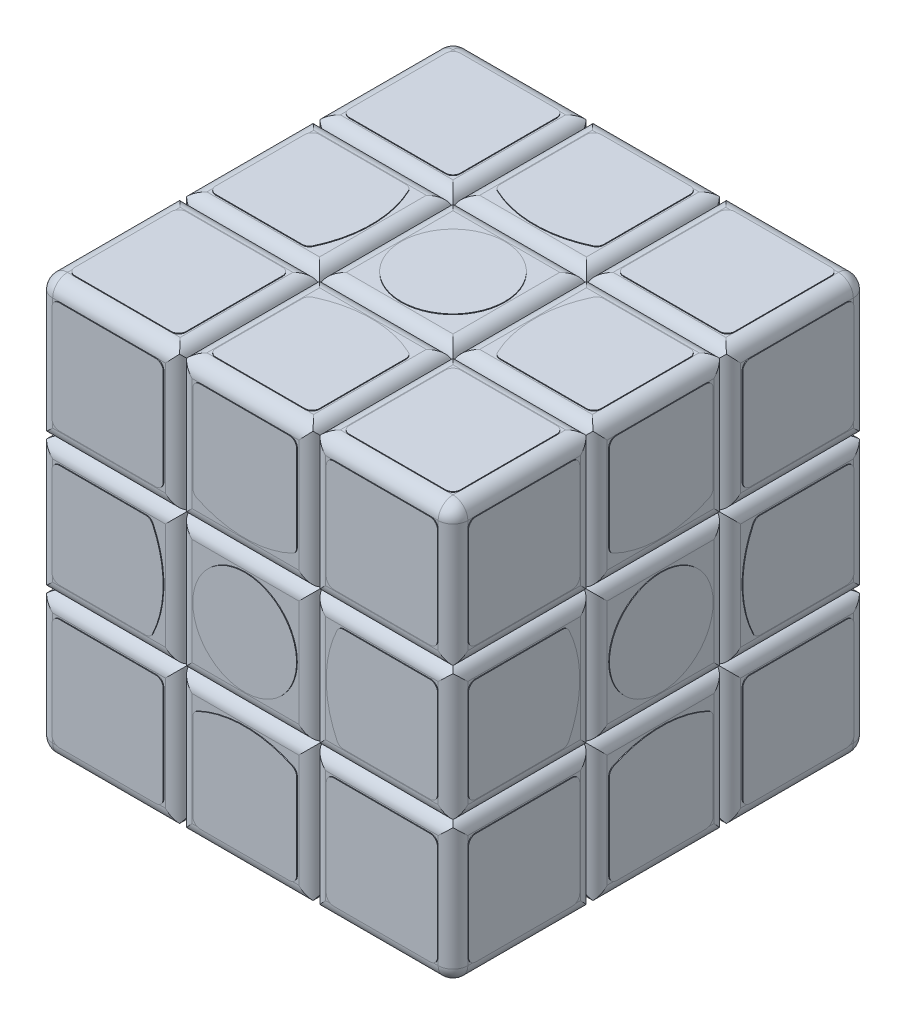
SolidWorks part; units mm, degrees
ref_plane "前视基准面" through (0, 0, 0) normal (0, 0, 1) x (1, 0, 0)
ref_plane "上视基准面" through (0, 0, 0) normal (0, 1, 0) x (1, 0, 0)
ref_plane "右视基准面" through (0, 0, 0) normal (1, 0, 0) x (0, 0, -1)
sketch "草图1" plane through (0, 0, 0) normal (0, 0, 1) x (1, 0, 0)
  line L5 (28, -28) -> (-28, -28)
  line L6 (28, -28) -> (28, 28)
  line L7 (28, 28) -> (-28, 28)
  line L8 (-28, -28) -> (-28, 28)
  line L9 (28, -28) -> (-28, 28) construction
  line L10 (28, 28) -> (-28, -28) construction
  point P0 (0, 0)
  dimension "D1" = 56
extrude "凸台-拉伸1" add sketch "草图1" along normal mid plane 56
fillet "圆角1" radius 2 12 edges at (0, 28, 28) (0, 28, -28) (28, 0, 28) (0, -28, 28) (-28, 0, 28) (0, -28, -28) (28, 0, -28) (-28, 0, -28) (28, 28, 0) (-28, 28, 0) (28, -28, 0) (-28, -28, 0)
sketch "草图2" plane through (0, 28, 0) normal (0, 1, 0) x (0, 0, -1)
  line L0 (0, 37.19) -> (0, -37.8051) construction
  line L1 (-9, 28) -> (-9, 9) construction
  line L2 (-26, 28) -> (26, 28) construction
  line L3 (-38.0373, 0) -> (42.2673, 0) construction
  line L5 (25, -7) -> (13.3509, -7)
  line L6 (-28, -26) -> (-28, 26) construction
  line L8 (-28, 9) -> (-9, 9) construction
  line L9 (25, 7) -> (13.3509, 7)
  line L10 (26, 6) -> (26, -6)
  line L11 (-28, 9) -> (-28, 26)
  line L18 (-26, 28) -> (-9, 28)
  line L19 (-25, 26) -> (-12, 26)
  line L20 (-11, 25) -> (-11, 12)
  line L21 (-25, 11) -> (-12, 11)
  line L26 (-26, 12) -> (-26, 25)
  line L27 (-11, 26) -> (-11, 11) construction
  line L28 (-26, 26) -> (-11, 26) construction
  line L29 (-26, 11) -> (-11, 11) construction
  line L51 (-26, 11) -> (-26, 26) construction
  line L52 (-7, -25) -> (-7, -13.3509)
  line L53 (12, 26) -> (25, 26)
  line L54 (11, 25) -> (11, 12)
  line L55 (25, 11) -> (12, 11)
  line L56 (26, 25) -> (26, 12)
  line L57 (26, -12) -> (26, -25)
  line L58 (25, -11) -> (12, -11)
  line L59 (11, -25) -> (11, -12)
  line L60 (25, -26) -> (12, -26)
  line L61 (-12, -26) -> (-25, -26)
  line L62 (-11, -25) -> (-11, -12)
  line L63 (-25, -11) -> (-12, -11)
  line L64 (-26, -25) -> (-26, -12)
  line L65 (26, 26) -> (-26, 26) construction
  line L66 (-6, 26) -> (6, 26)
  line L67 (-7, 25) -> (-7, 13.3509)
  line L69 (7, 25) -> (7, 13.3509)
  line L70 (7, -25) -> (7, -13.3509)
  line L71 (6, -26) -> (-6, -26)
  line L72 (-25, 7) -> (-13.3509, 7)
  line L73 (-25, -7) -> (-13.3509, -7)
  line L74 (-26, -6) -> (-26, 6)
  arc A38 (-11, 25) -> (-12, 26) centre (-12, 25) ccw
  arc A39 (-11, 12) -> (-12, 11) centre (-12, 12) cw
  arc A40 (-26, 12) -> (-25, 11) centre (-25, 12) ccw
  arc A41 (-26, 25) -> (-25, 26) centre (-25, 25) cw
  arc A42 (25, 26) -> (26, 25) centre (25, 25) cw
  arc A43 (12, 26) -> (11, 25) centre (12, 25) ccw
  arc A44 (12, 11) -> (11, 12) centre (12, 12) cw
  arc A45 (25, 11) -> (26, 12) centre (25, 12) ccw
  arc A46 (26, -25) -> (25, -26) centre (25, -25) cw
  arc A47 (26, -12) -> (25, -11) centre (25, -12) ccw
  arc A48 (11, -12) -> (12, -11) centre (12, -12) cw
  arc A49 (11, -25) -> (12, -26) centre (12, -25) ccw
  arc A50 (-25, -26) -> (-26, -25) centre (-25, -25) cw
  arc A51 (-12, -26) -> (-11, -25) centre (-12, -25) ccw
  arc A52 (-12, -11) -> (-11, -12) centre (-12, -12) cw
  arc A53 (-25, -11) -> (-26, -12) centre (-25, -12) ccw
  arc A55 (-6.4286, 12.4474) -> (6.4286, 12.4474) centre (0, 26) ccw
  arc A56 (-6.4286, 12.4474) -> (-7, 13.3509) centre (-6, 13.3509) cw
  arc A57 (7, 13.3509) -> (6.4286, 12.4474) centre (6, 13.3509) cw
  arc A58 (6, 26) -> (7, 25) centre (6, 25) cw
  arc A59 (-7, 25) -> (-6, 26) centre (-6, 25) cw
  arc A60 (26, -6) -> (25, -7) centre (25, -6) cw
  arc A61 (13.3509, -7) -> (12.4474, -6.4286) centre (13.3509, -6) cw
  arc A62 (12.4474, 6.4286) -> (12.4474, -6.4286) centre (26, 0) ccw
  arc A63 (12.4474, 6.4286) -> (13.3509, 7) centre (13.3509, 6) cw
  arc A64 (25, 7) -> (26, 6) centre (25, 6) cw
  arc A65 (-6, -26) -> (-7, -25) centre (-6, -25) cw
  arc A66 (-7, -13.3509) -> (-6.4286, -12.4474) centre (-6, -13.3509) cw
  arc A67 (6.4286, -12.4474) -> (-6.4286, -12.4474) centre (0, -26) ccw
  arc A68 (6.4286, -12.4474) -> (7, -13.3509) centre (6, -13.3509) cw
  arc A69 (7, -25) -> (6, -26) centre (6, -25) cw
  arc A70 (-26, 6) -> (-25, 7) centre (-25, 6) cw
  arc A71 (-13.3509, 7) -> (-12.4474, 6.4286) centre (-13.3509, 6) cw
  arc A72 (-12.4474, -6.4286) -> (-12.4474, 6.4286) centre (-26, 0) ccw
  arc A73 (-12.4474, -6.4286) -> (-13.3509, -7) centre (-13.3509, -6) cw
  arc A74 (-25, -7) -> (-26, -6) centre (-25, -6) cw
  circle A75 centre (0, 0) radius 7
  point P67 (0, 0)
  point P81 (-7, 26)
  point P124 (0, 0)
  dimension "D5" = 4
  dimension "D7" = 1
  dimension "D8" = 4
  dimension "D4" = 1
  dimension "D1" = 19
  dimension "D2" = 19
  dimension "D3" = 2
  dimension "D6" = 4
extrude "凸台-拉伸2" add sketch "草图2" along normal blind 0.1
sketch "草图4" plane through (28, 0, 0) normal (1, 0, 0) x (0, 0, -1)
  line L2 (-9, 28) -> (-9, 9) construction
  line L3 (-38.0373, 0) -> (42.2673, 0) construction
  line L4 (25, -7) -> (13.3509, -7)
  line L5 (-28, 9) -> (-9, 9) construction
  line L32 (25, 7) -> (13.3509, 7)
  line L33 (26, 6) -> (26, -6)
  line L34 (-25, 26) -> (-12, 26)
  line L35 (-11, 25) -> (-11, 12)
  line L36 (-25, 11) -> (-12, 11)
  line L37 (-26, 12) -> (-26, 25)
  line L38 (-7, -25) -> (-7, -13.3509)
  line L39 (12, 26) -> (25, 26)
  line L40 (11, 25) -> (11, 12)
  line L41 (25, 11) -> (12, 11)
  line L42 (26, 25) -> (26, 12)
  line L43 (26, -12) -> (26, -25)
  line L44 (25, -11) -> (12, -11)
  line L45 (11, -25) -> (11, -12)
  line L46 (25, -26) -> (12, -26)
  line L47 (-12, -26) -> (-25, -26)
  line L48 (-11, -25) -> (-11, -12)
  line L49 (-25, -11) -> (-12, -11)
  line L50 (-26, -25) -> (-26, -12)
  line L51 (-6, 26) -> (6, 26)
  line L52 (-7, 25) -> (-7, 13.3509)
  line L53 (7, 25) -> (7, 13.3509)
  line L54 (7, -25) -> (7, -13.3509)
  line L55 (6, -26) -> (-6, -26)
  line L56 (-25, 7) -> (-13.3509, 7)
  line L57 (-25, -7) -> (-13.3509, -7)
  line L58 (-26, -6) -> (-26, 6)
  arc A37 (-11, 25) -> (-12, 26) centre (-12, 25) ccw
  arc A38 (-11, 12) -> (-12, 11) centre (-12, 12) cw
  arc A39 (-26, 12) -> (-25, 11) centre (-25, 12) ccw
  arc A40 (-26, 25) -> (-25, 26) centre (-25, 25) cw
  arc A41 (25, 26) -> (26, 25) centre (25, 25) cw
  arc A42 (12, 26) -> (11, 25) centre (12, 25) ccw
  arc A43 (12, 11) -> (11, 12) centre (12, 12) cw
  arc A44 (25, 11) -> (26, 12) centre (25, 12) ccw
  arc A45 (26, -25) -> (25, -26) centre (25, -25) cw
  arc A46 (26, -12) -> (25, -11) centre (25, -12) ccw
  arc A47 (11, -12) -> (12, -11) centre (12, -12) cw
  arc A48 (11, -25) -> (12, -26) centre (12, -25) ccw
  arc A49 (-25, -26) -> (-26, -25) centre (-25, -25) cw
  arc A50 (-12, -26) -> (-11, -25) centre (-12, -25) ccw
  arc A51 (-12, -11) -> (-11, -12) centre (-12, -12) cw
  arc A52 (-25, -11) -> (-26, -12) centre (-25, -12) ccw
  arc A53 (-6.4286, 12.4474) -> (6.4286, 12.4474) centre (0, 26) ccw
  arc A54 (-6.4286, 12.4474) -> (-7, 13.3509) centre (-6, 13.3509) cw
  arc A55 (7, 13.3509) -> (6.4286, 12.4474) centre (6, 13.3509) cw
  arc A56 (6, 26) -> (7, 25) centre (6, 25) cw
  arc A57 (-7, 25) -> (-6, 26) centre (-6, 25) cw
  arc A58 (26, -6) -> (25, -7) centre (25, -6) cw
  arc A59 (13.3509, -7) -> (12.4474, -6.4286) centre (13.3509, -6) cw
  arc A60 (12.4474, 6.4286) -> (12.4474, -6.4286) centre (26, 0) ccw
  arc A61 (12.4474, 6.4286) -> (13.3509, 7) centre (13.3509, 6) cw
  arc A62 (25, 7) -> (26, 6) centre (25, 6) cw
  arc A63 (-6, -26) -> (-7, -25) centre (-6, -25) cw
  arc A64 (-7, -13.3509) -> (-6.4286, -12.4474) centre (-6, -13.3509) cw
  arc A65 (6.4286, -12.4474) -> (-6.4286, -12.4474) centre (0, -26) ccw
  arc A66 (6.4286, -12.4474) -> (7, -13.3509) centre (6, -13.3509) cw
  arc A67 (7, -25) -> (6, -26) centre (6, -25) cw
  arc A68 (-26, 6) -> (-25, 7) centre (-25, 6) cw
  arc A69 (-13.3509, 7) -> (-12.4474, 6.4286) centre (-13.3509, 6) cw
  arc A70 (-12.4474, -6.4286) -> (-12.4474, 6.4286) centre (-26, 0) ccw
  arc A71 (-12.4474, -6.4286) -> (-13.3509, -7) centre (-13.3509, -6) cw
  arc A72 (-25, -7) -> (-26, -6) centre (-25, -6) cw
  circle A73 centre (0, 0) radius 7
  point P56 (0, 0)
  point P108 (0, 0)
  dimension "D1" = 1
  dimension "D3" = 1
  dimension "D2" = 4
sketch "草图5" plane through (0, 0, -28) normal (0, 0, -1) x (-1, 0, 0)
  line L2 (0, 22.4404) -> (0, -52.5548) construction
  line L3 (-9, 28) -> (-9, 9) construction
  line L4 (-38.0373, 0) -> (42.2673, 0) construction
  line L5 (25, -7) -> (13.3509, -7)
  line L32 (-28, 9) -> (-9, 9) construction
  line L33 (25, 7) -> (13.3509, 7)
  line L34 (26, 6) -> (26, -6)
  line L37 (-25, 26) -> (-12, 26)
  line L38 (-11, 25) -> (-11, 12)
  line L39 (-25, 11) -> (-12, 11)
  line L40 (-26, 12) -> (-26, 25)
  line L41 (-7, -25) -> (-7, -13.3509)
  line L42 (12, 26) -> (25, 26)
  line L43 (11, 25) -> (11, 12)
  line L44 (25, 11) -> (12, 11)
  line L45 (26, 25) -> (26, 12)
  line L46 (26, -12) -> (26, -25)
  line L47 (25, -11) -> (12, -11)
  line L48 (11, -25) -> (11, -12)
  line L49 (25, -26) -> (12, -26)
  line L50 (-12, -26) -> (-25, -26)
  line L51 (-11, -25) -> (-11, -12)
  line L52 (-25, -11) -> (-12, -11)
  line L53 (-26, -25) -> (-26, -12)
  line L54 (-6, 26) -> (6, 26)
  line L55 (-7, 25) -> (-7, 13.3509)
  line L56 (7, 25) -> (7, 13.3509)
  line L57 (7, -25) -> (7, -13.3509)
  line L58 (6, -26) -> (-6, -26)
  line L59 (-25, 7) -> (-13.3509, 7)
  line L60 (-25, -7) -> (-13.3509, -7)
  line L61 (-26, -6) -> (-26, 6)
  arc A37 (-11, 25) -> (-12, 26) centre (-12, 25) ccw
  arc A38 (-11, 12) -> (-12, 11) centre (-12, 12) cw
  arc A39 (-26, 12) -> (-25, 11) centre (-25, 12) ccw
  arc A40 (-26, 25) -> (-25, 26) centre (-25, 25) cw
  arc A41 (25, 26) -> (26, 25) centre (25, 25) cw
  arc A42 (12, 26) -> (11, 25) centre (12, 25) ccw
  arc A43 (12, 11) -> (11, 12) centre (12, 12) cw
  arc A44 (25, 11) -> (26, 12) centre (25, 12) ccw
  arc A45 (26, -25) -> (25, -26) centre (25, -25) cw
  arc A46 (26, -12) -> (25, -11) centre (25, -12) ccw
  arc A47 (11, -12) -> (12, -11) centre (12, -12) cw
  arc A48 (11, -25) -> (12, -26) centre (12, -25) ccw
  arc A49 (-25, -26) -> (-26, -25) centre (-25, -25) cw
  arc A50 (-12, -26) -> (-11, -25) centre (-12, -25) ccw
  arc A51 (-12, -11) -> (-11, -12) centre (-12, -12) cw
  arc A52 (-25, -11) -> (-26, -12) centre (-25, -12) ccw
  arc A53 (-6.4286, 12.4474) -> (6.4286, 12.4474) centre (0, 26) ccw
  arc A54 (-6.4286, 12.4474) -> (-7, 13.3509) centre (-6, 13.3509) cw
  arc A55 (7, 13.3509) -> (6.4286, 12.4474) centre (6, 13.3509) cw
  arc A56 (6, 26) -> (7, 25) centre (6, 25) cw
  arc A57 (-7, 25) -> (-6, 26) centre (-6, 25) cw
  arc A58 (26, -6) -> (25, -7) centre (25, -6) cw
  arc A59 (13.3509, -7) -> (12.4474, -6.4286) centre (13.3509, -6) cw
  arc A60 (12.4474, 6.4286) -> (12.4474, -6.4286) centre (26, 0) ccw
  arc A61 (12.4474, 6.4286) -> (13.3509, 7) centre (13.3509, 6) cw
  arc A62 (25, 7) -> (26, 6) centre (25, 6) cw
  arc A63 (-6, -26) -> (-7, -25) centre (-6, -25) cw
  arc A64 (-7, -13.3509) -> (-6.4286, -12.4474) centre (-6, -13.3509) cw
  arc A65 (6.4286, -12.4474) -> (-6.4286, -12.4474) centre (0, -26) ccw
  arc A66 (6.4286, -12.4474) -> (7, -13.3509) centre (6, -13.3509) cw
  arc A67 (7, -25) -> (6, -26) centre (6, -25) cw
  arc A68 (-26, 6) -> (-25, 7) centre (-25, 6) cw
  arc A69 (-13.3509, 7) -> (-12.4474, 6.4286) centre (-13.3509, 6) cw
  arc A70 (-12.4474, -6.4286) -> (-12.4474, 6.4286) centre (-26, 0) ccw
  arc A71 (-12.4474, -6.4286) -> (-13.3509, -7) centre (-13.3509, -6) cw
  arc A72 (-25, -7) -> (-26, -6) centre (-25, -6) cw
  circle A73 centre (0, 0) radius 7
  point P60 (0, 0)
  point P112 (0, 0)
  dimension "D1" = 1
  dimension "D3" = 1
  dimension "D2" = 4
extrude "凸台-拉伸3" add sketch "草图5" along normal blind 0.1
extrude "凸台-拉伸4" add sketch "草图4" along normal blind 0.1
sketch "草图6" plane through (0, 28, 0) normal (0, 1, 0) x (1, 0, 0)
  line L0 (-9, 31.4185) -> (-9, 16.8061) construction
  line L8 (-12, 28) -> (-6, 28) construction
  line L25 (-10.8, 28) -> (-7.2, 28)
  line L26 (7.2, 28) -> (10.8, 28)
  line L27 (28, 10.8) -> (28, 7.2)
  line L28 (28, -7.2) -> (28, -10.8)
  line L29 (10.8, -28) -> (7.2, -28)
  line L30 (-7.2, -28) -> (-10.8, -28)
  line L31 (-28, -10.8) -> (-28, -7.2)
  line L32 (-28, 7.2) -> (-28, 10.8)
  arc A16 (-9, 26.2) -> (-10.8, 28) centre (-10.8, 26.2) ccw
  arc A17 (-9, 26.2) -> (-7.2, 28) centre (-7.2, 26.2) cw
  arc A18 (9, 26.2) -> (10.8, 28) centre (10.8, 26.2) cw
  arc A19 (9, 26.2) -> (7.2, 28) centre (7.2, 26.2) ccw
  arc A20 (26.2, 9) -> (28, 7.2) centre (26.2, 7.2) cw
  arc A21 (26.2, 9) -> (28, 10.8) centre (26.2, 10.8) ccw
  arc A22 (26.2, -9) -> (28, -10.8) centre (26.2, -10.8) cw
  arc A23 (26.2, -9) -> (28, -7.2) centre (26.2, -7.2) ccw
  arc A24 (9, -26.2) -> (7.2, -28) centre (7.2, -26.2) cw
  arc A25 (9, -26.2) -> (10.8, -28) centre (10.8, -26.2) ccw
  arc A26 (-9, -26.2) -> (-10.8, -28) centre (-10.8, -26.2) cw
  arc A27 (-9, -26.2) -> (-7.2, -28) centre (-7.2, -26.2) ccw
  arc A28 (-26.2, -9) -> (-28, -7.2) centre (-26.2, -7.2) cw
  arc A29 (-26.2, -9) -> (-28, -10.8) centre (-26.2, -10.8) ccw
  arc A30 (-26.2, 9) -> (-28, 10.8) centre (-26.2, 10.8) cw
  arc A31 (-26.2, 9) -> (-28, 7.2) centre (-26.2, 7.2) ccw
  point P51 (0, 0)
  dimension "D1" = 1.8
  dimension "D2" = 90
  dimension "D3" = 2
  dimension "D4" = 4
extrude "切除-拉伸1" cut sketch "草图6" against normal through all both and the other way through all contours L25 L0 A17 | A31 A30 L32 | A29 A28 L31 | A27 A26 L30 | A23 A22 L28 | A21 A20 L27
sketch "草图12" plane through (28, 0, 0) normal (1, 0, 0) x (0, 0, -1)
  line L0 (-10.8, 28) -> (-7.2, 28)
  line L1 (7.2, 28) -> (10.8, 28)
  line L2 (28, 10.8) -> (28, 7.2)
  line L3 (28, -7.2) -> (28, -10.8)
  line L12 (10.8, -28) -> (7.2, -28)
  line L13 (-7.2, -28) -> (-10.8, -28)
  line L14 (-28, -10.8) -> (-28, -7.2)
  line L15 (-28, 7.2) -> (-28, 10.8)
  arc A16 (-9, 26.2) -> (-10.8, 28) centre (-10.8, 26.2) ccw
  arc A17 (-9, 26.2) -> (-7.2, 28) centre (-7.2, 26.2) cw
  arc A18 (9, 26.2) -> (10.8, 28) centre (10.8, 26.2) cw
  arc A19 (9, 26.2) -> (7.2, 28) centre (7.2, 26.2) ccw
  arc A20 (26.2, 9) -> (28, 7.2) centre (26.2, 7.2) cw
  arc A21 (26.2, 9) -> (28, 10.8) centre (26.2, 10.8) ccw
  arc A22 (26.2, -9) -> (28, -10.8) centre (26.2, -10.8) cw
  arc A23 (26.2, -9) -> (28, -7.2) centre (26.2, -7.2) ccw
  arc A24 (9, -26.2) -> (7.2, -28) centre (7.2, -26.2) cw
  arc A25 (9, -26.2) -> (10.8, -28) centre (10.8, -26.2) ccw
  arc A26 (-9, -26.2) -> (-10.8, -28) centre (-10.8, -26.2) cw
  arc A27 (-9, -26.2) -> (-7.2, -28) centre (-7.2, -26.2) ccw
  arc A28 (-26.2, -9) -> (-28, -7.2) centre (-26.2, -7.2) cw
  arc A29 (-26.2, -9) -> (-28, -10.8) centre (-26.2, -10.8) ccw
  arc A30 (-26.2, 9) -> (-28, 10.8) centre (-26.2, 10.8) cw
  arc A31 (-26.2, 9) -> (-28, 7.2) centre (-26.2, 7.2) ccw
  point P40 (0, 0)
extrude "切除-拉伸12" cut sketch "草图12" against normal through all
sketch "草图13" plane through (0, 0, -28) normal (0, 0, -1) x (-1, 0, 0)
  line L0 (-10.8, 28) -> (-7.2, 28)
  line L1 (7.2, 28) -> (10.8, 28)
  line L2 (28, 10.8) -> (28, 7.2)
  line L3 (28, -7.2) -> (28, -10.8)
  line L12 (10.8, -28) -> (7.2, -28)
  line L13 (-7.2, -28) -> (-10.8, -28)
  line L14 (-28, -10.8) -> (-28, -7.2)
  line L15 (-28, 7.2) -> (-28, 10.8)
  arc A16 (-9, 26.2) -> (-10.8, 28) centre (-10.8, 26.2) ccw
  arc A17 (-9, 26.2) -> (-7.2, 28) centre (-7.2, 26.2) cw
  arc A18 (9, 26.2) -> (10.8, 28) centre (10.8, 26.2) cw
  arc A19 (9, 26.2) -> (7.2, 28) centre (7.2, 26.2) ccw
  arc A20 (26.2, 9) -> (28, 7.2) centre (26.2, 7.2) cw
  arc A21 (26.2, 9) -> (28, 10.8) centre (26.2, 10.8) ccw
  arc A22 (26.2, -9) -> (28, -10.8) centre (26.2, -10.8) cw
  arc A23 (26.2, -9) -> (28, -7.2) centre (26.2, -7.2) ccw
  arc A24 (9, -26.2) -> (7.2, -28) centre (7.2, -26.2) cw
  arc A25 (9, -26.2) -> (10.8, -28) centre (10.8, -26.2) ccw
  arc A26 (-9, -26.2) -> (-10.8, -28) centre (-10.8, -26.2) cw
  arc A27 (-9, -26.2) -> (-7.2, -28) centre (-7.2, -26.2) ccw
  arc A28 (-26.2, -9) -> (-28, -7.2) centre (-26.2, -7.2) cw
  arc A29 (-26.2, -9) -> (-28, -10.8) centre (-26.2, -10.8) ccw
  arc A30 (-26.2, 9) -> (-28, 10.8) centre (-26.2, 10.8) cw
  arc A31 (-26.2, 9) -> (-28, 7.2) centre (-26.2, 7.2) ccw
  point P40 (0, 0)
extrude "切除-拉伸11" cut sketch "草图13" against normal through all contours A16 A17 L0 | A19 A18 L1 | A21 A20 L2 | A23 A22 L3 | A25 A24 L12 | A27 A26 L13 | A31 A30 L15 | A29 A28 L14
mirror "镜向1" about plane through (0, 0, 0) normal (0, 0, 1) of "凸台-拉伸3"
mirror "镜向2" about plane through (0, 0, 0) normal (0, 1, 0) of "凸台-拉伸2"
mirror "镜向3" about plane through (0, 0, 0) normal (1, 0, 0) of "凸台-拉伸4"
sketch "草图14" plane through (28, 0, 0) normal (1, 0, 0) x (0, 0, -1)
  line L0 (4.3589, 9) -> (4.3589, 9.5683)
  line L1 (9, 13.3509) -> (9.2, 13.3509)
  line L2 (9.2, 13.3509) -> (9.2, 12)
  line L3 (9.2, 10.2) -> (9.2, 12)
  line L4 (12, 9.2) -> (10.2, 9.2)
  line L5 (12, 9.2) -> (13.3509, 9.2)
  line L6 (9, 13.3509) -> (9, 25)
  line L7 (6, 28) -> (-6, 28)
  line L8 (-9, 25) -> (-9, 13.3509)
  line L12 (13.3509, 9) -> (13.3509, 9.2)
  line L13 (9, 4.3589) -> (9.5683, 4.3589)
  line L14 (9, -4.3589) -> (9.5683, -4.3589)
  line L15 (13.3509, -9) -> (13.3509, -9.2)
  line L16 (13.3509, -9.2) -> (12, -9.2)
  line L17 (10.2, -9.2) -> (12, -9.2)
  line L18 (9.2, -12) -> (9.2, -10.2)
  line L19 (9.2, -12) -> (9.2, -13.3509)
  line L20 (-9.2, 12) -> (-9.2, 10.2)
  line L21 (9, -13.3509) -> (9.2, -13.3509)
  line L22 (4.3589, -9) -> (4.3589, -9.5683)
  line L23 (-4.3589, -9) -> (-4.3589, -9.5683)
  line L24 (-9, -13.3509) -> (-9.2, -13.3509)
  line L27 (-13.3509, 9.2) -> (-12, 9.2)
  line L28 (-9.2, 12) -> (-9.2, 13.3509)
  line L29 (-10.8, 10.8) -> (-9, 9) construction
  line L30 (-10.2, 9.2) -> (-12, 9.2)
  line L31 (-9.2, -13.3509) -> (-9.2, -12)
  line L32 (-9.2, -10.2) -> (-9.2, -12)
  line L33 (-12, -9.2) -> (-10.2, -9.2)
  line L37 (-13.3509, 9) -> (-13.3509, 9.2)
  line L38 (-9, 13.3509) -> (-9.2, 13.3509)
  line L39 (-12, -9.2) -> (-13.3509, -9.2)
  line L40 (-13.3509, -9) -> (-13.3509, -9.2)
  line L41 (-9, 4.3589) -> (-9.5683, 4.3589)
  line L42 (-4.3589, 9) -> (-4.3589, 9.5683)
  line L43 (-9, -4.3589) -> (-9.5683, -4.3589)
  arc A0 (9, 4.3589) -> (4.3589, 9) centre (0, 0) ccw
  arc A1 (4.3589, 9.5683) -> (7.2857, 10.6404) centre (0, 26) ccw
  arc A2 (7.2857, 10.6404) -> (9, 13.3509) centre (6, 13.3509) ccw
  arc A3 (-4.3589, 9) -> (-9, 4.3589) centre (0, 0) ccw
  arc A4 (9.2, 10.2) -> (10.2, 9.2) centre (10.2, 10.2) ccw
  arc A5 (13.3509, 9) -> (10.6404, 7.2857) centre (13.3509, 6) ccw
  arc A6 (10.6404, 7.2857) -> (9.5683, 4.3589) centre (26, 0) ccw
  arc A7 (4.3589, -9) -> (9, -4.3589) centre (0, 0) ccw
  arc A8 (9.5683, -4.3589) -> (10.6404, -7.2857) centre (26, 0) ccw
  arc A9 (10.6404, -7.2857) -> (13.3509, -9) centre (13.3509, -6) ccw
  arc A10 (10.2, -9.2) -> (9.2, -10.2) centre (10.2, -10.2) ccw
  arc A11 (9, -13.3509) -> (7.2857, -10.6404) centre (6, -13.3509) ccw
  arc A12 (7.2857, -10.6404) -> (4.3589, -9.5683) centre (0, -26) ccw
  arc A13 (-9, 13.3509) -> (-7.2857, 10.6404) centre (-6, 13.3509) ccw
  arc A14 (-7.2857, 10.6404) -> (7.2857, 10.6404) centre (0, 26) ccw
  arc A15 (7.2857, 10.6404) -> (9, 13.3509) centre (6, 13.3509) ccw
  arc A16 (9, 25) -> (6, 28) centre (6, 25) ccw
  arc A17 (-6, 28) -> (-9, 25) centre (-6, 25) ccw
  arc A18 (-9, 13.3509) -> (-7.2857, 10.6404) centre (-6, 13.3509) ccw
  arc A19 (-7.2857, 10.6404) -> (-4.3589, 9.5683) centre (0, 26) ccw
  arc A23 (-9, -4.3589) -> (-4.3589, -9) centre (0, 0) ccw
  arc A24 (-4.3589, -9.5683) -> (-7.2857, -10.6404) centre (0, -26) ccw
  arc A25 (-7.2857, -10.6404) -> (-9, -13.3509) centre (-6, -13.3509) ccw
  arc A26 (-9.2, -10.2) -> (-10.2, -9.2) centre (-10.2, -10.2) ccw
  arc A27 (-13.3509, -9) -> (-10.6404, -7.2857) centre (-13.3509, -6) ccw
  arc A28 (-10.6404, -7.2857) -> (-9.5683, -4.3589) centre (-26, 0) ccw
  arc A38 (-10.2, 9.2) -> (-9.2, 10.2) centre (-10.2, 10.2) ccw
  arc A41 (-9.5683, 4.3589) -> (-10.6404, 7.2857) centre (-26, 0) ccw
  arc A50 (-10.6404, 7.2857) -> (-13.3509, 9) centre (-13.3509, 6) ccw
  point P8 (-9.2, 9.2)
  point P92 (0, 0)
  dimension "D5" = 1
  dimension "D2" = 2
